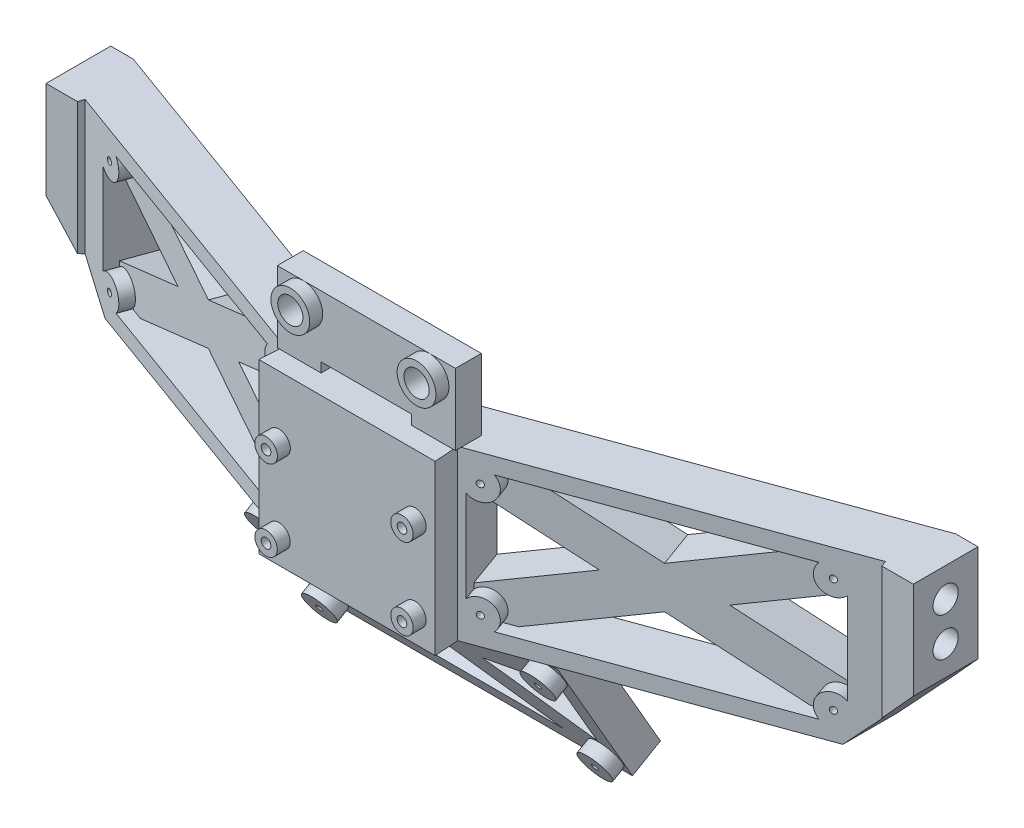
SolidWorks part; units mm, degrees
ref_plane "Ebene vorne" through (0, 0, 0) normal (0, 0, 1) x (1, 0, 0)
ref_plane "Ebene oben" through (0, 0, 0) normal (0, 1, 0) x (1, 0, 0)
ref_plane "Ebene rechts" through (0, 0, 0) normal (1, 0, 0) x (0, 0, -1)
sketch "Sketch1" plane through (0, 0, 0) normal (0, 0, 1) x (1, 0, 0)
  line L0 (0, 0) -> (0, 98) construction
  line L1 (-55, 98) -> (55, 98)
  line L2 (-70, 0) -> (70, 0)
  line L3 (-80, 78) -> (80, 78) construction
  line L4 (-80, 78) -> (-55, 98)
  line L5 (55, 98) -> (80, 78)
  line L6 (-70, 0) -> (-77.9327, 6.6563)
  line L7 (-80, 78) -> (-77.9327, 6.6563)
  line L8 (70, 0) -> (77.9327, 6.6563)
  line L9 (80, 78) -> (77.9327, 6.6563)
  line L10 (-78.5511, 28) -> (78.5511, 28) construction
  line L11 (-67.8317, 72.3671) -> (-50.7906, 86)
  line L12 (-50.7906, 86) -> (50.7906, 86)
  line L13 (50.7906, 86) -> (67.8317, 72.3671)
  line L14 (67.8317, 72.3671) -> (66.7419, 34.7553)
  line L15 (65.6324, 12) -> (66.0937, 12.3871)
  line L16 (-65.6324, 12) -> (65.6324, 12)
  line L17 (-65.6324, 12) -> (-66.0937, 12.3871)
  line L18 (-67.8317, 72.3671) -> (-66.7419, 34.7553)
  line L19 (-66.3561, 21.4447) -> (-66.0937, 12.3871)
  line L20 (-67.8317, 72.3671) -> (-66.0937, 12.3871) construction
  line L21 (66.3561, 21.4447) -> (66.0937, 12.3871)
  line L22 (67.8317, 72.3671) -> (66.0937, 12.3871) construction
  circle A0 centre (-70, 28) radius 6
  circle A1 centre (70, 28) radius 6
  arc A2 (-66.3561, 21.4447) -> (-66.7419, 34.7553) centre (-70, 28) ccw
  arc A3 (66.7419, 34.7553) -> (66.3561, 21.4447) centre (70, 28) ccw
  point P6 (0, 98)
  point P9 (0, 0)
  point P13 (0, 78)
  point P18 (0, 28)
  dimension "D11" = 12
  dimension "D16" = 15
  dimension "D1" = 110
  dimension "D2" = 98
  dimension "D3" = 140
  dimension "D4" = 160
  dimension "D5" = 140
  dimension "D6" = 20
  dimension "D7" = 127
  dimension "D8" = 140
  dimension "D9" = 127
  dimension "D10" = 28
  dimension "D12" = 70
  dimension "D14" = 70
  dimension "D15" = 12
extrude "Boss-Extrude1" add sketch "Sketch1" along normal blind 10
sketch "Sketch3" plane through (0, 0, 0) normal (0, 0, -1) x (-1, 0, 0)
  line L0 (0, 98) -> (0, 0) construction
  line L1 (-55, 98) -> (55, 98) construction
  line L2 (-79.1597, 49) -> (79.1597, 49) construction
  line L3 (80, 78) -> (77.9327, 6.6563) construction
  line L4 (-13.5, 64.75) -> (-67.611, 64.75)
  line L5 (10.5, 42.75) -> (-10.5, 42.75) construction
  line L6 (10.5, 42.75) -> (10.5, 55.25) construction
  line L7 (10.5, 55.25) -> (-10.5, 55.25) construction
  line L8 (-10.5, 42.75) -> (-10.5, 55.25) construction
  line L9 (-66.7419, 34.7553) -> (-67.8317, 72.3671) construction
  line L10 (-13.5, 38.75) -> (-66.8576, 38.75)
  line L11 (-13.5, 64.75) -> (13.5, 64.75)
  line L12 (-13.5, 64.75) -> (-13.5, 38.75) construction
  line L13 (-13.5, 38.75) -> (13.5, 38.75)
  line L14 (13.5, 64.75) -> (13.5, 38.75) construction
  line L15 (-66.8576, 38.75) -> (-67.611, 64.75)
  line L16 (13.5, 38.75) -> (66.8576, 38.75)
  line L17 (67.8317, 72.3671) -> (66.7419, 34.7553) construction
  line L18 (13.5, 64.75) -> (67.611, 64.75)
  line L19 (67.611, 64.75) -> (66.8576, 38.75)
  circle A0 centre (-10.5, 55.25) radius 0.75
  circle A1 centre (10.5, 55.25) radius 0.75
  circle A2 centre (10.5, 42.75) radius 0.75
  circle A3 centre (-10.5, 42.75) radius 0.75
  point P5 (0, 49)
  point P10 (0, 49)
  point P15 (0, 51.75)
  dimension "D6" = 1.5
  dimension "D1" = 21
  dimension "D2" = 12.5
  dimension "D3" = 26
  dimension "D4" = 27
  dimension "D5" = 9.5
extrude "Boss-Extrude2" add sketch "Sketch3" along normal blind 15 and the other way blind 25 separate body
sketch "Sketch5" plane through (0, 0, 25) normal (0, 0, 1) x (1, 0, 0)
  line L0 (-10.5, 56) -> (10.5, 42.75) construction
  line L1 (-67.611, 64.75) -> (67.611, 64.75) construction
  line L2 (-15, 34) -> (15, 34)
  line L3 (-15, 34) -> (-15, 64.75)
  line L4 (-15, 64.75) -> (15, 64.75)
  line L5 (15, 34) -> (15, 64.75)
  line L6 (-15, 34) -> (15, 64.75) construction
  line L7 (-15, 64.75) -> (15, 34) construction
  circle A0 centre (-10.5, 55.25) radius 0.75 construction
  point P5 (0, 49.375)
  dimension "D1" = 30
extrude "Cut-Extrude1" cut sketch "Sketch5" against normal blind 2.5
sketch "Sketch6" plane through (0, 64.75, 0) normal (0, 1, 0) x (1, 0, 0)
  line L9 (-67.611, -5) -> (-45.611, 15)
  line L10 (-67.611, -25) -> (-67.611, 15) construction
  line L11 (-67.611, 15) -> (67.611, 15) construction
  line L12 (-45.611, 15) -> (45.611, 15)
  line L13 (45.611, 15) -> (67.611, -5)
  line L14 (67.611, -25) -> (67.611, 15) construction
  line L15 (67.611, -5) -> (67.611, 32.366)
  line L16 (67.611, 32.366) -> (-67.611, 33.0215)
  line L17 (-67.611, 33.0215) -> (-67.611, -5)
  dimension "D1" = 22
  dimension "D2" = 22
ref_plane "Plane4" through (9.7895, 0, 26.8965) normal (0.342, 0, 0.9397) x (0, 1, 0)
ref_plane "Plane5" through (20.0501, 0, 55.0872) normal (0.342, 0, 0.9397) x (0, 1, 0)
ref_plane "Plane6" through (0, 16.1827, -28.0292) normal (0, -0.5, 0.866) x (-1, 0, 0)
ref_plane "Plane7" through (0, -1.3173, 2.2816) normal (0, -0.5, 0.866) x (-1, 0, 0)
sketch "Sketch14" plane through (0, -1.3173, 2.2816) normal (0, -0.5, 0.866) x (-1, 0, 0)
  line L0 (0, -44.8085) -> (0, -18.1493) construction
  line L1 (15, -44.8085) -> (-15, -44.8085) construction
  line L2 (-66.8576, -26.0585) -> (66.8576, -26.0585) construction
  line L3 (-25, -38.7585) -> (25, -38.7585)
  line L4 (-25, -38.7585) -> (-25, -13.3585)
  line L5 (-25, -13.3585) -> (25, -13.3585)
  line L6 (25, -38.7585) -> (25, -13.3585)
  line L7 (-25, -38.7585) -> (25, -13.3585) construction
  line L8 (-25, -13.3585) -> (25, -38.7585) construction
  point P5 (0, -26.0585)
  dimension "D1" = 50
  dimension "D2" = 25.4
extrude "Boss-Extrude5" add sketch "Sketch14" against normal blind 38
sketch "Sketch10" plane through (20.0501, 0, 55.0872) normal (0.342, 0, 0.9397) x (0, 1, 0)
  line L0 (38.75, -5.5449) -> (64.75, -5.5449) construction
  line L1 (42.75, -1.4665) -> (42.75, -86.1407) construction
  line L3 (41.25, -9.5449) -> (62.25, -9.5449)
  line L4 (41.25, -9.5449) -> (41.25, -55.5449)
  line L5 (41.25, -55.5449) -> (62.25, -55.5449)
  line L6 (62.25, -9.5449) -> (62.25, -55.5449)
  line L7 (41.25, -9.5449) -> (62.25, -55.5449) construction
  line L8 (41.25, -55.5449) -> (62.25, -9.5449) construction
  ellipse E0 centre (42.75, -2.1713) end of major axis (43.5, -2.1713) minor radius 0.7048 construction
  point P12 (51.75, -32.5449)
  dimension "D1" = 21
  dimension "D2" = 46
  dimension "D3" = 1.5
  dimension "D4" = 4
extrude "Cut-Extrude3" cut sketch "Sketch10" against normal blind 48
sketch "Sketch16" plane through (0, 33.5658, 19.3792) normal (0, 0.866, 0.5) x (1, 0, 0)
  line L1 (-25, -2.6346) -> (23, -2.6346)
  line L2 (-25, -2.6346) -> (-25, 4.9587)
  line L3 (-25, 4.9587) -> (23, 4.9587)
  line L4 (23, -2.6346) -> (23, 4.9587)
  dimension "D1" = 48
extrude "Boss-Extrude6" add sketch "Sketch16" along normal blind 4
extrude "Cut-Extrude6" cut sketch "Sketch5<2>" against normal blind 2.5 and the other way blind 4
sketch "Sketch5<2>" plane through (0, 0, 25) normal (0, 0, 1) x (1, 0, 0) same geometry as "Sketch5"
mirror "Mirror1" about plane through (0, 0, 0) normal (1, 0, 0) of "Cut-Extrude3"
sketch "Sketch11" plane through (0, 64.75, 0) normal (0, 1, 0) x (1, 0, 0)
  line L0 (-67.611, -10) -> (-15, -25)
  line L1 (-55, -10) -> (-80, -10) construction
  line L2 (-67.611, -25) -> (-67.611, -10) construction
  line L3 (-15, -25) -> (15, -25)
  line L4 (6.9237, -27.9395) -> (12.6553, -25.8534) construction
  line L5 (15, -25) -> (67.611, -25) construction
  line L6 (15, -25) -> (67.611, -10)
  line L7 (67.611, -25) -> (67.611, -10) construction
  line L8 (80, -10) -> (55, -10) construction
  line L9 (67.611, -10) -> (67.611, -47.0975)
  line L10 (67.611, -47.0975) -> (-67.611, -47.0975)
  line L11 (-67.611, -47.0975) -> (-67.611, -10)
extrude "Cut-Extrude4" cut sketch "Sketch11" against normal blind 40
sketch "Sketch12" plane through (3.6331, 0, 9.982) normal (0.342, 0, 0.9397) x (0.9397, 0, -0.342)
  line L0 (9.5449, 62.25) -> (55.5449, 41.25) construction
  line L2 (11.2599, 42.96) -> (53.8299, 42.96) construction
  line L3 (11.2599, 42.96) -> (11.2599, 60.54) construction
  line L4 (11.2599, 60.54) -> (53.8299, 60.54) construction
  line L5 (53.8299, 42.96) -> (53.8299, 60.54) construction
  line L6 (11.2599, 42.96) -> (53.8299, 60.54) construction
  line L7 (11.2599, 60.54) -> (53.8299, 42.96) construction
  circle A0 centre (11.2599, 60.54) radius 0.5
  circle A1 centre (53.8299, 60.54) radius 0.5
  circle A2 centre (53.8299, 42.96) radius 0.5
  circle A3 centre (11.2599, 42.96) radius 0.5
  circle A4 centre (11.2599, 60.54) radius 2.4218
  circle A5 centre (53.8299, 60.54) radius 2.4218
  circle A6 centre (53.8299, 42.96) radius 2.4218
  circle A7 centre (11.2599, 42.96) radius 2.4218
  point P4 (32.5449, 51.75)
  dimension "D3" = 1
  dimension "D1" = 42.57
  dimension "D2" = 17.58
extrude "Boss-Extrude4" add sketch "Sketch12" along normal blind 5
sketch "Sketch13" plane through (3.6331, 0, 9.982) normal (0.342, 0, 0.9397) x (0.9397, 0, -0.342)
  circle A0 centre (53.8299, 60.54) radius 0.5 construction
  circle A1 centre (53.8299, 42.96) radius 0.5 construction
  circle A2 centre (11.2599, 42.96) radius 0.5 construction
  circle A3 centre (11.2599, 60.54) radius 0.5 construction
  circle A4 centre (53.8299, 60.54) radius 0.5
  circle A5 centre (53.8299, 42.96) radius 0.5
  circle A6 centre (11.2599, 42.96) radius 0.5
  circle A7 centre (11.2599, 60.54) radius 0.5
extrude "Cut-Extrude5" cut sketch "Sketch13" against normal blind 15
mirror "Mirror2" about plane through (0, 0, 0) normal (1, 0, 0) of "Boss-Extrude4", "Cut-Extrude5"
sketch "Sketch18" plane through (0, 11.5688, 6.6792) normal (0, -0.866, -0.5) x (1, 0, 0)
  line L4 (25, -0.8624) -> (-25, -0.8624)
  line L5 (-25, -0.8624) -> (-25, -35.3654)
  line L6 (-25, -35.3654) -> (25, -35.3654)
  line L7 (25, -35.3654) -> (25, -0.8624)
  line L9 (-25, -0.8624) -> (-25, -35.3654)
  line L10 (-25, -35.3654) -> (25, -35.3654)
  line L11 (25, -35.3654) -> (25, -0.8624)
  line L12 (25, -0.8624) -> (-25, -0.8624)
  dimension "D1" = 0
extrude "Boss-Extrude7" add sketch "Sketch18" along normal blind 2.5
sketch "Sketch20" plane through (25, 0, 0) normal (1, 0, 0) x (0, 0, -1)
  line L0 (15, 44.75) -> (15, 38.75)
  line L1 (15, 38.75) -> (8.0512, 17.1867)
  line L2 (25.1981, 27.0864) -> (-0.9324, 12) construction
  line L3 (8.0512, 17.1867) -> (32.3738, 22.7236)
  line L4 (32.3738, 22.7236) -> (24.8679, 46.8252)
  line L5 (24.8679, 46.8252) -> (15, 44.75)
extrude "Cut-Extrude10" cut sketch "Sketch20" against normal through all
sketch "Sketch21" plane through (0, 0, 10) normal (0, 0, 1) x (1, 0, 0)
  line L8 (80, 78) -> (55, 98)
  line L9 (55, 98) -> (-55, 98)
  line L10 (-55, 98) -> (-80, 78)
  line L11 (-80, 78) -> (-77.9327, 6.6563)
  line L12 (-77.9327, 6.6563) -> (-70, 0)
  line L13 (-70, 0) -> (70, 0)
  line L14 (70, 0) -> (77.9327, 6.6563)
  line L15 (77.9327, 6.6563) -> (80, 78)
  line L16 (80, 78) -> (55, 98)
  line L17 (55, 98) -> (-55, 98)
  line L18 (-55, 98) -> (-80, 78)
  line L19 (-80, 78) -> (-77.9327, 6.6563)
  line L20 (-77.9327, 6.6563) -> (-70, 0)
  line L21 (-70, 0) -> (70, 0)
  line L22 (70, 0) -> (77.9327, 6.6563)
  line L23 (77.9327, 6.6563) -> (80, 78)
  line L30 (-67.611, 64.75) -> (-66.8576, 38.75)
  line L31 (-67.8317, 72.3671) -> (-67.611, 64.75)
  line L32 (-50.7906, 86) -> (-67.8317, 72.3671)
  line L33 (50.7906, 86) -> (-50.7906, 86)
  line L34 (67.8317, 72.3671) -> (50.7906, 86)
  line L35 (67.611, 64.75) -> (67.8317, 72.3671)
  line L36 (-67.611, 64.75) -> (-66.8576, 38.75)
  line L37 (66.8576, 38.75) -> (67.611, 64.75)
  line L38 (66.0937, 12.3871) -> (66.3561, 21.4447)
  line L39 (65.6324, 12) -> (66.0937, 12.3871)
  line L40 (-65.6324, 12) -> (65.6324, 12)
  line L41 (-66.0937, 12.3871) -> (-65.6324, 12)
  line L42 (-66.3561, 21.4447) -> (-66.0937, 12.3871)
  line L43 (66.8576, 38.75) -> (67.611, 64.75)
  line L45 (-67.8317, 72.3671) -> (-67.611, 64.75)
  line L46 (-50.7906, 86) -> (-67.8317, 72.3671)
  line L47 (50.7906, 86) -> (-50.7906, 86)
  line L48 (67.8317, 72.3671) -> (50.7906, 86)
  line L49 (67.611, 64.75) -> (67.8317, 72.3671)
  line L52 (66.0937, 12.3871) -> (66.3561, 21.4447)
  line L53 (65.6324, 12) -> (66.0937, 12.3871)
  line L54 (-65.6324, 12) -> (65.6324, 12)
  line L55 (-66.0937, 12.3871) -> (-65.6324, 12)
  line L56 (-66.3561, 21.4447) -> (-66.0937, 12.3871)
  line L58 (66.7419, 34.7553) -> (66.8576, 38.75)
  line L59 (66.7419, 34.7553) -> (66.8576, 38.75)
  line L60 (-66.8576, 38.75) -> (-66.7419, 34.7553)
  line L61 (-66.8576, 38.75) -> (-66.7419, 34.7553)
  arc A2 (66.7419, 34.7553) -> (66.3561, 21.4447) centre (70, 28) ccw
  arc A3 (-66.3561, 21.4447) -> (-66.7419, 34.7553) centre (-70, 28) ccw
  arc A4 (66.7419, 34.7553) -> (66.3561, 21.4447) centre (70, 28) ccw
  arc A5 (-66.3561, 21.4447) -> (-66.7419, 34.7553) centre (-70, 28) ccw
  dimension "D1" = 0
  dimension "D2" = 0
extrude "Cut-Extrude12" cut sketch "Sketch21" against normal through all
sketch "Sketch26" plane through (0, 64.75, 0) normal (0, 1, 0) x (1, 0, 0)
  line L0 (0, 15) -> (0, -22.5) construction
  line L1 (-45.611, 15) -> (45.611, 15) construction
  line L2 (15, -22.5) -> (-15, -22.5) construction
  line L3 (0, -8.12) -> (-103.0816, 29.3987)
  line L4 (0, -8.12) -> (100.1912, 28.3466)
  line L5 (-103.0816, 29.3987) -> (100.1912, 28.3466)
  dimension "D1" = 70
  dimension "D2" = 70
  dimension "D3" = 14.38
extrude "Cut-Extrude17" cut sketch "Sketch26" against normal up to next
sketch "Sketch27" plane through (-25, 0, 0) normal (-1, 0, 0) x (0, 0, 1)
  line L0 (-0.9793, 38.75) -> (29.2454, 38.75)
  line L1 (29.2454, 38.75) -> (32.7883, 8.7446)
  line L2 (32.7883, 8.7446) -> (-21.0748, 9.1321)
  line L3 (-21.0748, 9.1321) -> (-0.9793, 38.75)
extrude "Cut-Extrude20" cut sketch "Sketch27" against normal through all
sketch "Sketch28" plane through (-5.3432, 0, 14.6805) normal (-0.342, 0, 0.9397) x (0.9397, 0, 0.342)
  line L1 (-5.5449, 38.75) -> (-60.1134, 38.75)
  line L2 (-5.5449, 38.75) -> (-5.5449, 64.75)
  line L3 (-5.5449, 64.75) -> (-60.1134, 64.75)
  line L4 (-60.1134, 38.75) -> (-60.1134, 64.75)
extrude "Cut-Extrude21" cut sketch "Sketch28" along normal through all
mirror "Mirror3" about plane through (0, 0, 0) normal (1, 0, 0) of "Cut-Extrude21"
sketch "Sketch29" plane through (0, 64.75, 0) normal (0, 1, 0) x (1, 0, 0)
  line L0 (-14.0901, -22.5) -> (-13.3728, -11.7579)
  line L1 (-10.5537, -12.784) -> (-61.8313, 5.8795) construction
  line L2 (-13.3728, -11.7579) -> (-10.5537, -12.784)
  line L3 (-10.5537, -12.784) -> (-14.0901, -22.5)
  line L4 (0, 7.0342) -> (0, -29.1122) construction
  line L5 (13.3728, -11.7579) -> (10.5537, -12.784)
  line L6 (14.0901, -22.5) -> (13.3728, -11.7579)
  line L7 (10.5537, -12.784) -> (14.0901, -22.5)
  dimension "D1" = 3
extrude "Boss-Extrude9" add sketch "Sketch29" against normal up to surface (26 mm away) up to face at (0, 38.75, 1.753)
sketch "Sketch31" plane through (3.6331, 0, 9.982) normal (0.342, 0, 0.9397) x (0.9397, 0, -0.342)
  line L4 (9.5449, 58.83) -> (9.5449, 44.67)
  line L5 (12.9749, 41.25) -> (52.1149, 41.25)
  line L6 (55.5449, 44.67) -> (55.5449, 58.83)
  line L7 (52.1149, 62.25) -> (12.9749, 62.25)
  line L8 (9.5449, 58.83) -> (9.5449, 44.67)
  line L9 (12.9749, 41.25) -> (52.1149, 41.25)
  line L10 (55.5449, 44.67) -> (55.5449, 58.83)
  line L11 (52.1149, 62.25) -> (12.9749, 62.25)
  arc A4 (12.9749, 41.25) -> (9.5449, 44.67) centre (11.2599, 42.96) ccw
  arc A5 (55.5449, 44.67) -> (52.1149, 41.25) centre (53.8299, 42.96) ccw
  arc A6 (52.1149, 62.25) -> (55.5449, 58.83) centre (53.8299, 60.54) ccw
  arc A7 (9.5449, 58.83) -> (12.9749, 62.25) centre (11.2599, 60.54) ccw
  arc A8 (12.9749, 41.25) -> (9.5449, 44.67) centre (11.2599, 42.96) ccw
  arc A9 (55.5449, 44.67) -> (52.1149, 41.25) centre (53.8299, 42.96) ccw
  arc A10 (52.1149, 62.25) -> (55.5449, 58.83) centre (53.8299, 60.54) ccw
  arc A11 (9.5449, 58.83) -> (12.9749, 62.25) centre (11.2599, 60.54) ccw
  dimension "D1" = 0
extrude "Cut-Extrude22" cut sketch "Sketch31" against normal through all
mirror "Mirror4" about plane through (0, 0, 0) normal (1, 0, 0) of "Cut-Extrude22"
sketch "Sketch30" plane through (-5.3432, 0, 14.6805) normal (-0.342, 0, 0.9397) x (0.9397, 0, 0.342)
  line L0 (-53.8299, 60.54) -> (-36.4747, 53.3729) construction
  line L3 (-55.5449, 58.0025) -> (-40.4045, 51.75)
  line L6 (-55.5449, 58.83) -> (-55.5449, 44.67) construction
  line L7 (-52.1149, 41.25) -> (-12.9749, 41.25) construction
  line L8 (-9.5449, 45.4975) -> (-24.6853, 51.75)
  line L9 (-9.5449, 44.67) -> (-9.5449, 58.83) construction
  line L10 (-12.9749, 62.25) -> (-52.1149, 62.25) construction
  line L11 (-53.8299, 42.96) -> (-36.4747, 50.1271) construction
  line L12 (-9.5449, 58.0025) -> (-24.6853, 51.75)
  line L13 (-55.5449, 45.4975) -> (-40.4045, 51.75)
  line L14 (-32.5449, 54.9957) -> (-14.9787, 62.25)
  line L15 (-28.6151, 50.1271) -> (-11.2599, 42.96) construction
  line L16 (-28.6151, 53.3729) -> (-11.2599, 60.54) construction
  line L17 (-32.5449, 54.9957) -> (-50.1111, 62.25)
  line L18 (-32.5449, 48.5043) -> (-50.1111, 41.25)
  line L19 (-32.5449, 48.5043) -> (-14.9787, 41.25)
  line L20 (-52.1149, 62.25) -> (-50.1111, 62.25)
  line L21 (-55.5449, 58.0025) -> (-55.5449, 58.83)
  line L22 (-55.5449, 45.4975) -> (-55.5449, 44.67)
  line L23 (-52.1149, 41.25) -> (-50.1111, 41.25)
  line L24 (-14.9787, 41.25) -> (-12.9749, 41.25)
  line L25 (-9.5449, 44.67) -> (-9.5449, 45.4975)
  line L26 (-9.5449, 58.0025) -> (-9.5449, 58.83)
  line L27 (-12.9749, 62.25) -> (-14.9787, 62.25)
  arc A3 (-12.9749, 62.25) -> (-9.5449, 58.83) centre (-11.2599, 60.54) ccw construction
  arc A4 (-9.5449, 44.67) -> (-12.9749, 41.25) centre (-11.2599, 42.96) ccw construction
  arc A5 (-52.1149, 41.25) -> (-55.5449, 44.67) centre (-53.8299, 42.96) ccw construction
  arc A6 (-55.5449, 58.83) -> (-52.1149, 62.25) centre (-53.8299, 60.54) ccw construction
  arc A7 (-12.9749, 62.25) -> (-9.5449, 58.83) centre (-11.2599, 60.54) ccw
  arc A8 (-9.5449, 44.67) -> (-12.9749, 41.25) centre (-11.2599, 42.96) ccw
  arc A9 (-52.1149, 41.25) -> (-55.5449, 44.67) centre (-53.8299, 42.96) ccw
  arc A10 (-55.5449, 58.83) -> (-52.1149, 62.25) centre (-53.8299, 60.54) ccw
  dimension "D1" = 3
  dimension "D2" = 3
  dimension "D3" = 3
  dimension "D4" = 3
extrude "Boss-Extrude11" add sketch "Sketch30" against normal up to surface (7.9923 mm away) up to face at (-11.25, 55.25, 4.0253)
extrude "Cut-Extrude23" cut sketch "Sketch30<2>" against normal blind 2
sketch "Sketch30<2>" plane through (-5.3432, 0, 14.6805) normal (-0.342, 0, 0.9397) x (0.9397, 0, 0.342) same geometry as "Sketch30"
sketch "Sketch32" plane through (5.3432, 0, 14.6805) normal (0.342, 0, 0.9397) x (0.9397, 0, -0.342)
  line L0 (11.2599, 60.54) -> (53.8299, 42.96) construction
  line L1 (14.9787, 62.25) -> (55.5449, 45.4975)
  line L2 (12.9749, 62.25) -> (52.1149, 62.25) construction
  line L3 (55.5449, 58.83) -> (55.5449, 44.67) construction
  line L4 (50.1111, 41.25) -> (9.5449, 58.0025)
  line L5 (52.1149, 41.25) -> (12.9749, 41.25) construction
  line L6 (9.5449, 44.67) -> (9.5449, 58.83) construction
  line L7 (11.2599, 42.96) -> (53.8299, 60.54) construction
  line L8 (55.5449, 58.0025) -> (14.9787, 41.25)
  line L9 (9.5449, 45.4975) -> (50.1111, 62.25)
  line L10 (9.5449, 58.0025) -> (9.5449, 58.83)
  line L11 (12.9749, 62.25) -> (14.9787, 62.25)
  line L12 (50.1111, 62.25) -> (52.1149, 62.25)
  line L13 (55.5449, 58.83) -> (55.5449, 58.0025)
  line L14 (55.5449, 45.4975) -> (55.5449, 44.67)
  line L15 (50.1111, 41.25) -> (52.1149, 41.25)
  line L16 (14.9787, 41.25) -> (12.9749, 41.25)
  line L17 (9.5449, 44.67) -> (9.5449, 45.4975)
  arc A0 (12.9749, 41.25) -> (9.5449, 44.67) centre (11.2599, 42.96) ccw construction
  arc A1 (55.5449, 44.67) -> (52.1149, 41.25) centre (53.8299, 42.96) ccw construction
  arc A2 (52.1149, 62.25) -> (55.5449, 58.83) centre (53.8299, 60.54) ccw construction
  arc A3 (9.5449, 58.83) -> (12.9749, 62.25) centre (11.2599, 60.54) ccw construction
  arc A4 (12.9749, 41.25) -> (9.5449, 44.67) centre (11.2599, 42.96) ccw
  arc A5 (55.5449, 44.67) -> (52.1149, 41.25) centre (53.8299, 42.96) ccw
  arc A6 (52.1149, 62.25) -> (55.5449, 58.83) centre (53.8299, 60.54) ccw
  arc A7 (9.5449, 58.83) -> (12.9749, 62.25) centre (11.2599, 60.54) ccw
  arc M11 (12.9749, 41.25) -> (9.5449, 44.67) centre (11.2599, 42.96) ccw
  line M12 (9.5449, 44.67) -> (9.5449, 58.83)
  arc M13 (9.5449, 58.83) -> (12.9749, 62.25) centre (11.2599, 60.54) ccw
  line M14 (12.9749, 62.25) -> (52.1149, 62.25)
  arc M15 (52.1149, 62.25) -> (55.5449, 58.83) centre (53.8299, 60.54) ccw
  line M16 (55.5449, 58.83) -> (55.5449, 44.67)
  arc M17 (55.5449, 44.67) -> (52.1149, 41.25) centre (53.8299, 42.96) ccw
  line M18 (52.1149, 41.25) -> (12.9749, 41.25)
  dimension "D1" = 3
  dimension "D2" = 3
  dimension "D3" = 3
  dimension "D4" = 3
extrude "Boss-Extrude12" add sketch "Sketch32" against normal up to surface (7.9923 mm away) contours L4 L9 L1 M14 M13 M12 | L9 L1 L8 M16 M15 M14 | L9 L4 L8 L1 | L9 L8 L4 M12 M11 M18 | L1 L8 L4 M18 M17 M16 region at (24.906, 56.7326, 7.5602) region at (46.9449, 56.7326, -0.4613) region at (35.9254, 51.75, 3.5495) region at (46.9449, 46.7674, -0.4613) region at (24.906, 46.7674, 7.5602) up to face at (33.1919, 51.75, -3.9609)
extrude "Cut-Extrude24" cut sketch "Sketch32<4>" against normal blind 2 contours L4 L9 L1 M14 M13 M12 | L9 L4 L8 L1 | L9 L1 L8 M16 M15 M14 | L1 L8 L4 M18 M17 M16 | L9 L8 L4 M12 M11 M18 region at (24.906, 56.7326, 7.5602) region at (46.9449, 56.7326, -0.4613) region at (35.9254, 51.75, 3.5495) region at (46.9449, 46.7674, -0.4613) region at (24.906, 46.7674, 7.5602)
sketch "Sketch32<4>" plane through (5.3432, 0, 14.6805) normal (0.342, 0, 0.9397) x (0.9397, 0, -0.342) same geometry as "Sketch32"
ref_plane "Plane8" through (0, -0.0553, 0.0958) normal (0, -0.5, 0.866) x (1, 0, 0)
ref_plane "Plane9" through (0, 8.9447, -15.4927) normal (0, -0.5, 0.866) x (1, 0, 0)
sketch "Sketch33" plane through (0, 8.9447, -15.4927) normal (0, -0.5, 0.866) x (1, 0, 0)
  line L0 (0, 44.8085) -> (0, 13.5384) construction
  line L1 (-14.0901, 44.8085) -> (14.0901, 44.8085) construction
  line L3 (-24, 36.1185) -> (24, 36.1185)
  line L4 (-24, 36.1185) -> (-24, 13.1185)
  line L5 (-24, 13.1185) -> (24, 13.1185)
  line L6 (24, 36.1185) -> (24, 13.1185)
  line L7 (-24, 36.1185) -> (24, 13.1185) construction
  line L8 (-24, 13.1185) -> (24, 36.1185) construction
  point P5 (0, 24.6185)
  dimension "D1" = 48
  dimension "D2" = 23
  dimension "D3" = 13
extrude "Boss-Extrude13" add sketch "Sketch33" along normal blind 5
sketch "Sketch34" plane through (0, 6.4447, -11.1626) normal (0, -0.5, 0.866) x (1, 0, 0)
  line L0 (-24, 36.1185) -> (24, 13.1185) construction
  line L2 (-21.285, 15.8285) -> (21.285, 15.8285) construction
  line L3 (-21.285, 15.8285) -> (-21.285, 33.4085) construction
  line L4 (-21.285, 33.4085) -> (21.285, 33.4085) construction
  line L5 (21.285, 15.8285) -> (21.285, 33.4085) construction
  line L6 (-21.285, 15.8285) -> (21.285, 33.4085) construction
  line L7 (-21.285, 33.4085) -> (21.285, 15.8285) construction
  circle A0 centre (-21.285, 33.4085) radius 0.5
  circle A1 centre (-21.285, 15.8285) radius 0.5
  circle A2 centre (21.285, 15.8285) radius 0.5
  circle A3 centre (21.285, 33.4085) radius 0.5
  circle A4 centre (-21.285, 33.4085) radius 2.5
  circle A5 centre (-21.285, 15.8285) radius 2.5
  circle A6 centre (21.285, 15.8285) radius 2.5
  circle A7 centre (21.285, 33.4085) radius 2.5
  point P4 (0, 24.6185)
  dimension "D3" = 1
  dimension "D4" = 5
  dimension "D1" = 42.57
  dimension "D2" = 17.58
extrude "Boss-Extrude14" add sketch "Sketch34" along normal blind 2
sketch "Sketch35" plane through (0, 0, 22.5) normal (0, 0, 1) x (1, 0, 0)
  line L4 (-14.0901, 38.75) -> (14.0901, 38.75)
  line L5 (14.0901, 38.75) -> (14.0901, 64.75)
  line L6 (14.0901, 64.75) -> (-14.0901, 64.75)
  line L7 (-14.0901, 64.75) -> (-14.0901, 38.75)
  line L8 (-14.0901, 38.75) -> (14.0901, 38.75)
  line L9 (14.0901, 38.75) -> (14.0901, 64.75)
  line L10 (14.0901, 64.75) -> (-14.0901, 64.75)
  line L11 (-14.0901, 64.75) -> (-14.0901, 38.75)
  circle A8 centre (-10.5, 55.25) radius 1.75
  circle A9 centre (10.5, 55.25) radius 1.7365
  circle A10 centre (10.5, 42.75) radius 1.7365
  circle A11 centre (-10.5, 42.75) radius 1.7365
  dimension "D1" = 3.5
  dimension "D2" = 0
extrude "Cut-Extrude25" cut sketch "Sketch35" against normal blind 5
sketch "Sketch36" plane through (0, 6.4447, -11.1626) normal (0, -0.5, 0.866) x (1, 0, 0)
  line L2 (-14.7353, 33.4085) -> (0, 27.3233)
  line L3 (14.7353, 15.8285) -> (0, 21.9137)
  line L4 (-21.285, 18.5333) -> (-6.5497, 24.6185)
  line L5 (21.285, 30.7037) -> (6.5497, 24.6185)
  line L6 (0, 27.3233) -> (14.7353, 33.4085)
  line L8 (0, 21.9137) -> (-14.7353, 15.8285)
  line L9 (6.5497, 24.6185) -> (21.285, 18.5333)
  line L11 (-6.5497, 24.6185) -> (-21.285, 30.7037)
  line L12 (14.7353, 15.8285) -> (-14.7353, 15.8285)
  line L13 (21.285, 18.5333) -> (21.285, 30.7037)
  line L14 (14.7353, 33.4085) -> (-14.7353, 33.4085)
  line L15 (-21.285, 30.7037) -> (-21.285, 18.5333)
  circle A0 centre (-21.285, 33.4085) radius 2.5 construction
extrude "Cut-Extrude27" cut sketch "Sketch36" against normal through all
sketch "Sketch37" plane through (0, 0, 22.5) normal (0, 0, 1) x (1, 0, 0)
  circle A0 centre (-10.5, 55.25) radius 0.75 construction
  circle A1 centre (10.5, 42.75) radius 0.75 construction
  circle A2 centre (10.5, 42.75) radius 1.7365 construction
  circle A3 centre (10.5, 55.25) radius 1.7365 construction
  circle A4 centre (10.5, 55.25) radius 0.75 construction
  circle A5 centre (-10.5, 42.75) radius 0.75 construction
  circle A6 centre (-10.5, 42.75) radius 1.7365 construction
  circle A7 centre (-10.5, 55.25) radius 1.75 construction
  circle A8 centre (-10.5, 55.25) radius 0.75
  circle A9 centre (10.5, 42.75) radius 0.75
  circle A10 centre (10.5, 42.75) radius 1.7365
  circle A11 centre (10.5, 55.25) radius 1.7365
  circle A12 centre (10.5, 55.25) radius 0.75
  circle A13 centre (-10.5, 42.75) radius 0.75
  circle A14 centre (-10.5, 42.75) radius 1.7365
  circle A15 centre (-10.5, 55.25) radius 1.75
extrude "Cut-Extrude28" cut sketch "Sketch37" against normal blind 3
sketch "Sketch38" plane through (-24, 0, 0) normal (-1, 0, 0) x (0, 0, 1)
  line L0 (5.12, 38.75) -> (6.8967, 37.7242)
  line L1 (6.8967, 37.7242) -> (7.93, 38.75)
  line L2 (7.93, 38.75) -> (5.12, 38.75)
extrude "Boss-Extrude15" add sketch "Sketch38" against normal up to surface (48 mm away) up to face at (24, 30.6671, 0.0391)
sketch "Sketch39" plane through (0, 38.75, 0) normal (0, 1, 0) x (1, 0, 0)
  line L0 (0, -8.12) -> (-15.258, -2.5665)
  line L1 (-15.258, -2.5665) -> (15.258, -2.5665)
  line L2 (15.258, -2.5665) -> (0, -8.12)
extrude "Boss-Extrude16" add sketch "Sketch39" along normal up to vertex (1.4742 mm away) up to point (15.258, 40.2242, 2.5665)
sketch "Sketch40" plane through (0, 64.75, 0) normal (0, 1, 0) x (1, 0, 0)
  line L11 (-67.611, -10) -> (-67.611, 5)
  line L12 (-67.611, -10) -> (-67.611, 15) construction
  line L13 (-67.611, 5) -> (-62.1515, 5)
  line L14 (-67.611, -10) -> (-61.8313, 5.8795) construction
  line L15 (-62.1515, 5) -> (-67.611, -10)
  line L16 (67.611, -10) -> (67.611, 5)
  line L17 (67.611, -10) -> (67.611, 15) construction
  line L18 (67.611, 5) -> (62.1515, 5)
  line L19 (67.611, -10) -> (61.8313, 5.8795) construction
  line L20 (62.1515, 5) -> (67.611, -10)
  dimension "D1" = 10
  dimension "D2" = 10
extrude "Cut-Extrude29" cut sketch "Sketch40" against normal through all
sketch "Sketch43" plane through (0, 0, -15) normal (0, 0, -1) x (-1, 0, 0)
  line L0 (-66.8576, 38.75) -> (-66.8576, 64.75)
  line L1 (-63.5217, 64.75) -> (-67.611, 64.75) construction
  line L2 (-66.8576, 64.75) -> (-67.611, 64.75)
  line L3 (-67.611, 64.75) -> (-66.8576, 38.75)
  line L4 (66.8576, 38.75) -> (66.8576, 64.75)
  line L5 (67.611, 64.75) -> (63.5217, 64.75) construction
  line L6 (66.8576, 64.75) -> (67.611, 64.75)
  line L7 (67.611, 64.75) -> (66.8576, 38.75)
extrude "Cut-Extrude32" cut sketch "Sketch43" against normal through all
sketch "Sketch45" plane through (0, 64.75, 0) normal (0, 1, 0) x (1, 0, 0)
  line L0 (0, 0) -> (0, 22.0417) construction
  line L1 (-67, 15) -> (-66.8576, 15)
  line L2 (-66.8576, 15) -> (-63.5217, 15) construction
  line L3 (66.8576, 15) -> (67, 15)
  line L4 (-67, 15) -> (-66.8576, 15)
  line L5 (-67, 15) -> (-67, 5)
  line L6 (-67, 5) -> (-66.8576, 5)
  line L7 (-66.8576, 15) -> (-66.8576, 5)
  line L8 (67, 15) -> (66.8576, 15)
  line L9 (67, 15) -> (67, 5)
  line L10 (67, 5) -> (66.8576, 5)
  line L11 (66.8576, 15) -> (66.8576, 5)
  point P6 (0, 15)
  line M2 (66.8576, 5) -> (66.8576, 15)
  line M7 (-66.8576, 15) -> (-66.8576, 5)
  dimension "D1" = 134
extrude "Boss-Extrude17" add sketch "Sketch45" against normal up to surface (26 mm away) contours L10 L9 L3 M2 | L5 L6 L1 M7 region at (-66.9288, 64.75, -10) region at (66.9288, 64.75, -10) up to face at (-48.352, 38.75, -4.3198)
sketch "Sketch47" plane through (0, 0, -15) normal (0, 0, -1) x (-1, 0, 0)
  line L0 (57, 38.75) -> (67, 49.75)
  line L1 (63.5217, 38.75) -> (17.5965, 38.75) construction
  line L2 (67, 38.75) -> (67, 64.75) construction
  line L3 (67, 64.75) -> (63.5217, 64.75) construction
  line L4 (67, 49.75) -> (67, 38.75)
  line L5 (67, 38.75) -> (57, 38.75)
  line L6 (0, 40.2242) -> (0, 64.75) construction
  line L7 (-67, 38.75) -> (-57, 38.75)
  line L8 (-67, 49.75) -> (-67, 38.75)
  line L9 (-57, 38.75) -> (-67, 49.75)
  dimension "D1" = 15
  dimension "D2" = 10
extrude "Cut-Extrude37" cut sketch "Sketch47" against normal through all
sketch "Sketch48" plane through (0, 0, 17.5) normal (0, 0, 1) x (1, 0, 0)
  line L0 (13.7562, 64.75) -> (-13.7562, 64.75) construction
  line L1 (-13.7562, 64.75) -> (-7, 64.75)
  line L2 (-13.7562, 64.75) -> (-13.7562, 78.25)
  line L3 (-13.7562, 78.25) -> (13.7562, 78.25)
  line L4 (13.7562, 64.75) -> (13.7562, 78.25)
  line L5 (0, 78.25) -> (0, 38.75) construction
  line L6 (23.8899, 38.75) -> (-23.8899, 38.75) construction
  line L7 (7, 64.75) -> (13.7562, 64.75)
  line L9 (7, 64.75) -> (7, 66.25)
  line L10 (7, 66.25) -> (-7, 66.25)
  line L11 (-7, 64.75) -> (-7, 66.25)
  line L12 (7, 64.75) -> (-7, 66.25) construction
  line L13 (7, 66.25) -> (-7, 64.75) construction
  point P11 (0, 65.5)
  dimension "D1" = 13.5
  dimension "D2" = 14
  dimension "D3" = 1.5
extrude "Boss-Extrude18" add sketch "Sketch48" against normal blind 4 from offset 5 offset against normal yes
sketch "Sketch49" plane through (0, 38.75, 0) normal (0, -1, 0) x (1, 0, 0)
  line L8 (13.4224, 12.5) -> (13.7562, 12.5)
  line L9 (13.7562, 12.5) -> (13.7562, 11.6184)
  line L10 (13.7562, 11.6184) -> (13.3728, 11.7579)
  line L11 (13.3728, 11.7579) -> (13.4224, 12.5)
  line L12 (-13.7562, 12.5) -> (-13.4224, 12.5)
  line L13 (-13.4224, 12.5) -> (-13.3728, 11.7579)
  line L14 (-13.3728, 11.7579) -> (-13.7562, 11.6184)
  line L15 (-13.7562, 11.6184) -> (-13.7562, 12.5)
sketch "Sketch50" plane through (0, 0, 17.5) normal (0, 0, 1) x (1, 0, 0)
  line L0 (-13.7562, 72.75) -> (13.7562, 72.75) construction
  line L1 (-13.7562, 38.75) -> (-13.7562, 64.75) construction
  line L2 (13.7562, 64.75) -> (13.7562, 38.75) construction
  line L3 (13.7562, 78.25) -> (-13.7562, 78.25) construction
  line L4 (0, 78.25) -> (0, 62.852) construction
  line L5 (-9.75, 72.75) -> (9.75, 72.75) construction
  circle A0 centre (-9.75, 72.75) radius 1.95
  circle A1 centre (9.75, 72.75) radius 1.95
  circle A2 centre (9.75, 72.75) radius 3
  circle A3 centre (-9.75, 72.75) radius 3
  point P16 (0, 72.75)
  dimension "D2" = 3.9
  dimension "D4" = 6
  dimension "D5" = 6
  dimension "D1" = 5.5
  dimension "D3" = 19.5
extrude "Boss-Extrude19" add sketch "Sketch50" along normal blind 2 from surface starting at face at (0, 67.75, 12.5)
sketch "Sketch51" plane through (0, 0, 17.5) normal (0, 0, 1) x (1, 0, 0)
  circle A0 centre (9.75, 72.75) radius 1.95 construction
  circle A1 centre (-9.75, 72.75) radius 1.95 construction
  circle A2 centre (9.75, 72.75) radius 1.95
  circle A3 centre (-9.75, 72.75) radius 1.95
extrude "Cut-Extrude39" cut sketch "Sketch51" against normal through all
sketch "Sketch52" plane through (0, 0, 17.5) normal (0, 0, 1) x (1, 0, 0)
  circle A0 centre (-10.5, 55.25) radius 0.75 construction
  circle A1 centre (10.5, 55.25) radius 0.75 construction
  circle A2 centre (10.5, 42.75) radius 0.75 construction
  circle A3 centre (-10.5, 42.75) radius 0.75 construction
  circle A4 centre (-10.5, 55.25) radius 0.75
  circle A5 centre (10.5, 55.25) radius 0.75
  circle A6 centre (10.5, 42.75) radius 0.75
  circle A7 centre (-10.5, 42.75) radius 0.75
extrude "Cut-Extrude40" cut sketch "Sketch52" against normal through all
sketch "Sketch55" plane through (-67, 0, 0) normal (-1, 0, 0) x (0, 0, 1)
  line L0 (-10, 64.75) -> (-10, 49.75) construction
  line L1 (-15, 64.75) -> (-5, 64.75) construction
  line L2 (-5, 49.75) -> (-15, 49.75) construction
  circle A0 centre (-10, 60.25) radius 1.95
  circle A1 centre (-10, 54.25) radius 1.95
  dimension "D1" = 3.9
  dimension "D2" = 4.5
  dimension "D3" = 6
extrude "Cut-Extrude42" cut sketch "Sketch55" against normal blind 10
extrude "Cut-Extrude43" cut sketch "Sketch55<2>" along normal blind 10 from surface starting at face at (67, 57.25, -10)
sketch "Sketch55<2>" plane through (-67, 0, 0) normal (-1, 0, 0) x (0, 0, 1) same geometry as "Sketch55"
sketch "Sketch56" plane through (0, 0, 17.5) normal (0, 0, 1) x (1, 0, 0)
  line L4 (-13.7562, 38.75) -> (13.7562, 38.75)
  line L5 (13.7562, 38.75) -> (13.7562, 64.75)
  line L6 (13.7562, 64.75) -> (-13.7562, 64.75)
  line L7 (-13.7562, 64.75) -> (-13.7562, 38.75)
  line L8 (-13.7562, 38.75) -> (13.7562, 38.75)
  line L9 (13.7562, 38.75) -> (13.7562, 64.75)
  line L10 (13.7562, 64.75) -> (-13.7562, 64.75)
  line L11 (-13.7562, 64.75) -> (-13.7562, 38.75)
  circle A0 centre (-10.5, 42.75) radius 1.7365 construction
  circle A1 centre (10.5, 42.75) radius 1.7365 construction
  circle A2 centre (10.5, 55.25) radius 1.7365 construction
  circle A3 centre (-10.5, 55.25) radius 1.75 construction
  circle A4 centre (-10.5, 42.75) radius 1.7365
  circle A5 centre (10.5, 42.75) radius 1.7365
  circle A6 centre (10.5, 55.25) radius 1.7365
  circle A7 centre (-10.5, 55.25) radius 1.75
  dimension "D1" = 0
extrude "Cut-Extrude44" cut sketch "Sketch56" against normal blind 2
sketch "Sketch57" plane through (0, 0, 19.5) normal (0, 0, 1) x (1, 0, 0)
  circle A0 centre (10.5, 55.25) radius 1.7365 construction
  circle A1 centre (10.5, 42.75) radius 1.7365 construction
  circle A2 centre (-10.5, 42.75) radius 1.7365 construction
  circle A3 centre (-10.5, 55.25) radius 1.75 construction
  circle A4 centre (10.5, 55.25) radius 1.7365
  circle A5 centre (10.5, 42.75) radius 1.7365
  circle A6 centre (-10.5, 42.75) radius 1.7365
  circle A7 centre (-10.5, 55.25) radius 1.75
extrude "Cut-Extrude45" cut sketch "Sketch57" against normal blind 2
sketch "Sketch58" plane through (0, 0, 12.5) normal (0, 0, 1) x (1, 0, 0)
  line L0 (0, 78.25) -> (0, 66.25) construction
  line L1 (13.7562, 78.25) -> (-13.7562, 78.25) construction
  line L2 (-7, 66.25) -> (7, 66.25) construction
  line L9 (-13.7562, 75.75) -> (13.7562, 75.75)
  line L10 (13.7562, 64.75) -> (13.7562, 78.25) construction
  line L11 (13.7562, 75.75) -> (13.7562, 78.25)
  line L12 (13.7562, 78.25) -> (-13.7562, 78.25)
  line L13 (-13.7562, 78.25) -> (-13.7562, 75.75)
  circle A1 centre (9.75, 72.75) radius 3 construction
  point P11 (0, 75.75)
extrude "Cut-Extrude46" cut sketch "Sketch58" against normal through all
